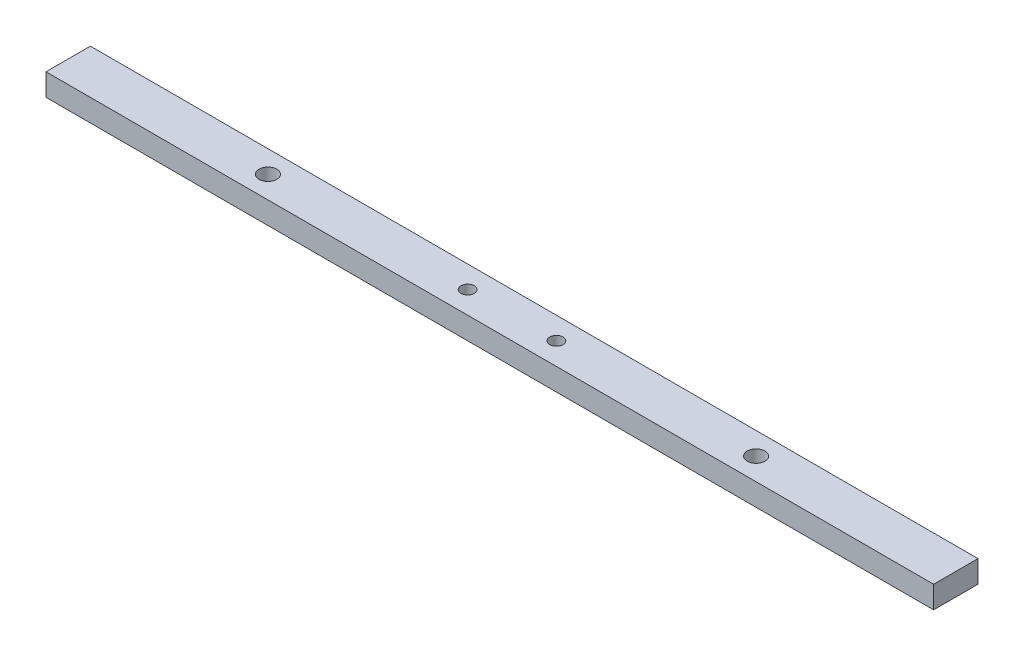
SolidWorks part; units mm, degrees
ref_plane "Plan de face" through (0, 0, 0) normal (0, 0, 1) x (1, 0, 0)
ref_plane "Plan de dessus" through (0, 0, 0) normal (0, 1, 0) x (1, 0, 0)
ref_plane "Plan de droite" through (0, 0, 0) normal (1, 0, 0) x (0, 0, -1)
sketch "Esquisse1" plane through (0, 0, 0) normal (0, 0, 1) x (1, 0, 0)
  line L0 (0, 0) -> (200, 0)
  line L1 (0, 0) -> (0, -5)
  line L2 (200, 0) -> (200, -5)
  line L3 (0, -5) -> (200, -5)
  dimension "D1" = 200
  dimension "D2" = 5
extrude "Boss.-Extru.1" add sketch "Esquisse1" along normal blind 10
sketch "Esquisse2" plane through (0, 0, 10) normal (0, 0, 1) x (1, 0, 0)
  line L0 (100, 0) -> (155, 0) construction
  line L1 (200, 0) -> (0, 0) construction
  line L2 (100, 0) -> (45, 0) construction
  line L3 (100, 0) -> (90, 0) construction
  line L4 (100, 0) -> (110, 0) construction
  line L5 (45, 0) -> (45, -5) construction
  line L6 (0, -5) -> (200, -5) construction
  line L7 (90, 0) -> (90, -5) construction
  line L8 (100, 0) -> (100, -5) construction
  line L9 (110, 0) -> (110, -5) construction
  line L10 (155, 0) -> (155, -5) construction
  dimension "D1" = 55
  dimension "D2" = 55
  dimension "D3" = 10
  dimension "D4" = 10
sketch "Esquisse3" plane through (0, -5, 0) normal (0, -1, 0) x (1, 0, 0)
  line L0 (45, 10) -> (45, 0) construction
  line L1 (0, 0) -> (200, 0) construction
  line L2 (90, 10) -> (90, 0) construction
  line L3 (110, 10) -> (110, 0) construction
  line L4 (155, 10) -> (155, 0) construction
  circle A0 centre (45, 5) radius 2
  circle A1 centre (155, 5) radius 2
  circle A2 centre (110, 5) radius 1.5
  circle A3 centre (90, 5) radius 1.5
  dimension "D1" = 4
  dimension "D2" = 3
extrude "Enlèv. mat.-Extru.1" cut sketch "Esquisse3" against normal blind 10 contours A0
extrude "Enlèv. mat.-Extru.2" cut sketch "Esquisse3<4>" against normal blind 10
sketch "Esquisse3<4>" plane through (0, -5, 0) normal (0, -1, 0) x (1, 0, 0) same geometry as "Esquisse3"
